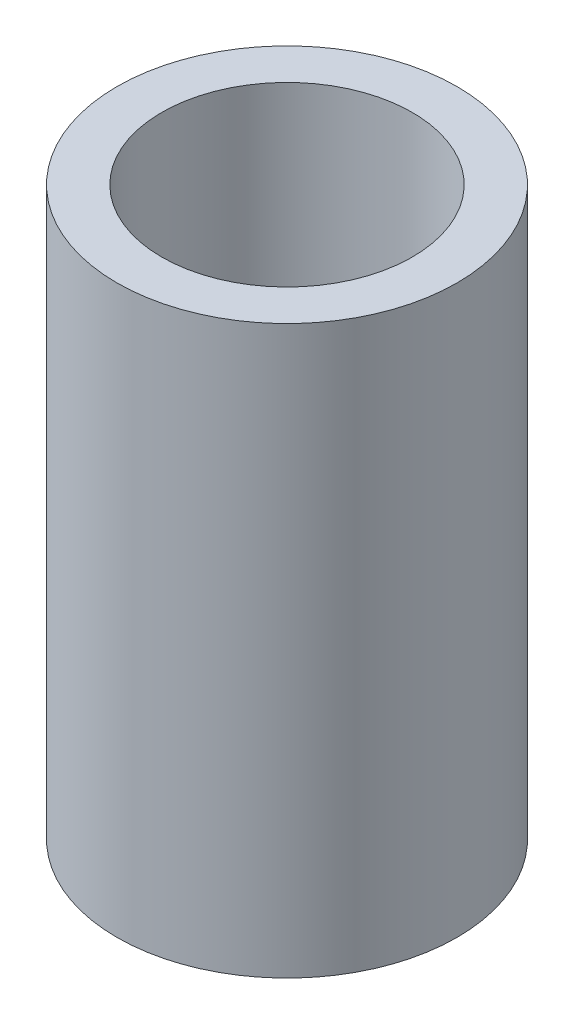
SolidWorks part; units mm, degrees
ref_plane "Front Plane" through (0, 0, 0) normal (0, 0, 1) x (1, 0, 0)
ref_plane "Top Plane" through (0, 0, 0) normal (0, 1, 0) x (1, 0, 0)
ref_plane "Right Plane" through (0, 0, 0) normal (1, 0, 0) x (0, 0, -1)
sketch "Sketch1" plane through (0, 0, 0) normal (0, 1, 0) x (1, 0, 0)
  circle A0 centre (0, 0) radius 2.85
  circle A1 centre (0, 0) radius 2.1
  dimension "D1" = 4.2
  dimension "D2" = 5.7
extrude "Boss-Extrude1" add sketch "Sketch1" along normal blind 9.5
